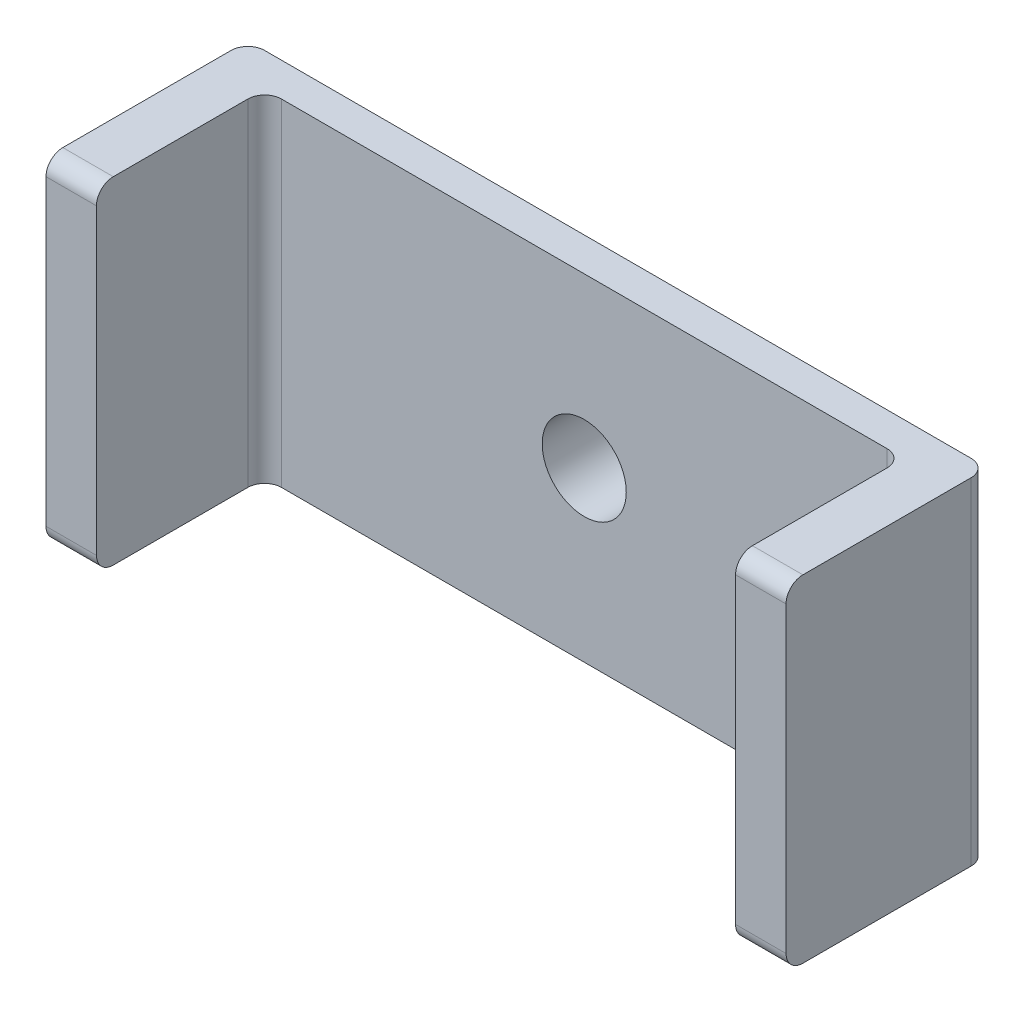
SolidWorks part; units mm, degrees
ref_plane "前视基准面" through (0, 0, 0) normal (0, 0, 1) x (1, 0, 0)
ref_plane "上视基准面" through (0, 0, 0) normal (0, 1, 0) x (1, 0, 0)
ref_plane "右视基准面" through (0, 0, 0) normal (1, 0, 0) x (0, 0, -1)
sketch "草图1" plane through (0, 0, 0) normal (0, 0, 1) x (1, 0, 0)
  line L1 (110, 50) -> (-110, 50)
  line L2 (110, 50) -> (110, -50)
  line L3 (110, -50) -> (-110, -50)
  line L4 (-110, 50) -> (-110, -50)
  line L5 (0, -50) -> (0, 50) construction
  line L6 (110, 0) -> (-110, 0) construction
  circle A0 centre (0, 0) radius 12.5
  point P0 (0, 0)
  dimension "D1" = 220
  dimension "D2" = 100
extrude "拉伸-薄壁1" add sketch "草图1" against normal blind 15 thin contours A0 thin type one direction wall 2
extrude "凸台-拉伸1" add sketch "草图1<3>" along normal blind 10
sketch "草图1<3>" plane through (0, 0, 0) normal (0, 0, 1) x (1, 0, 0) same geometry as "草图1"
sketch "草图2" plane through (0, 0, 10) normal (0, 0, 1) x (1, 0, 0)
  line L0 (-110, -50) -> (110, -50) construction
  line L1 (-110, 50) -> (-95, 50)
  line L2 (-110, 50) -> (-110, -50)
  line L3 (-110, -50) -> (-95, -50)
  line L4 (-95, 50) -> (-95, -50)
  line L6 (110, 50) -> (95, 50)
  line L7 (110, 50) -> (110, -50)
  line L8 (110, -50) -> (95, -50)
  line L9 (95, 50) -> (95, -50)
extrude "凸台-拉伸2" add sketch "草图2" along normal blind 50
fillet "圆角1" radius 5 8 edges at (-110, 0, 0) (110, 0, 0) (95, 0, 10) (-95, 0, 10) (102.5, 50, 60) (102.5, -50, 60) (-102.5, -50, 60) (-102.5, 50, 60)
